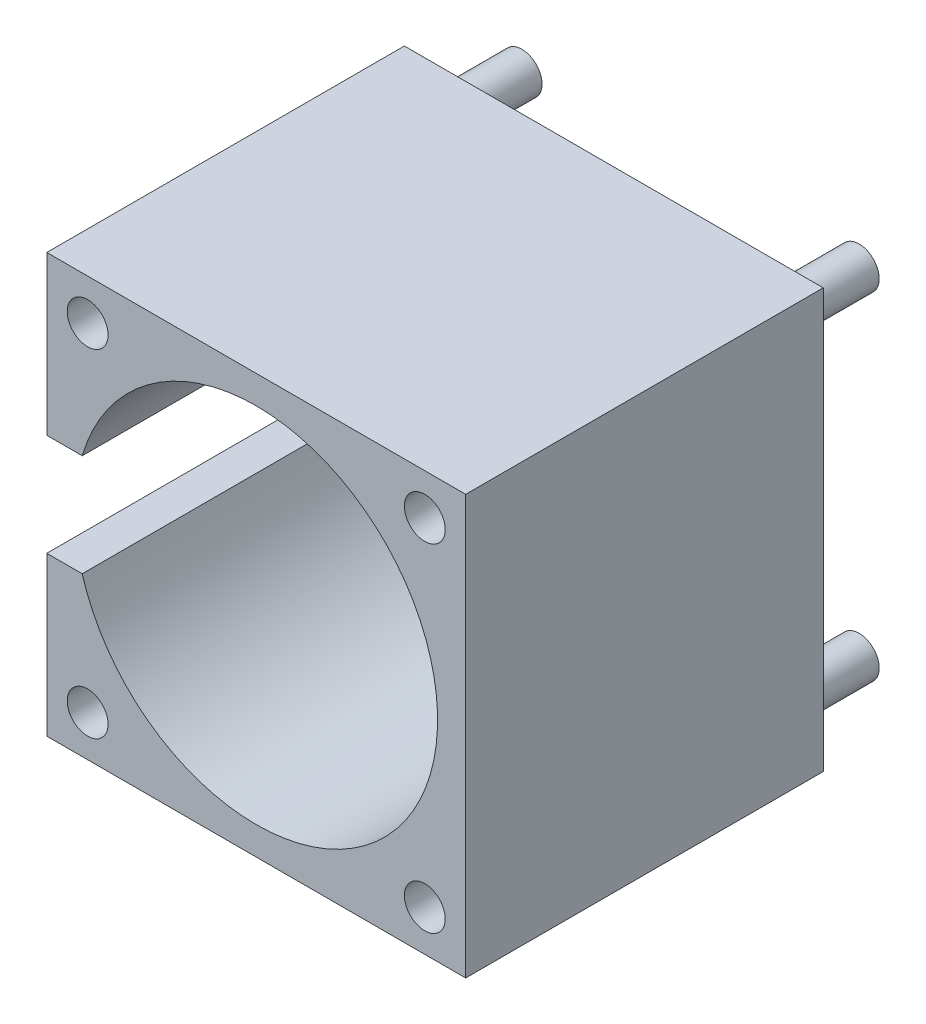
SolidWorks part; units mm, degrees
ref_plane "前基準面" through (0, 0, 0) normal (0, 0, 1) x (1, 0, 0)
ref_plane "上基準面" through (0, 0, 0) normal (0, 1, 0) x (1, 0, 0)
ref_plane "右基準面" through (0, 0, 0) normal (1, 0, 0) x (0, 0, -1)
ref_axis "基準軸1" through (0, -55, 0) along (0, 1, 0)
ref_axis "基準軸2" through (-88.99, 0, 0) along (1, 0, 0)
ref_axis "基準軸3" through (0, 0, 55) along (0, 0, -1)
sketch "草圖1" plane through (0, 0, 0) normal (0, 0, 1) x (1, 0, 0)
  line L0 (0, -55) -> (0, 55) construction
  line L1 (-41, -41) -> (41, -41)
  line L2 (-41, -41) -> (-41, 41)
  line L3 (-41, 41) -> (41, 41)
  line L4 (41, -41) -> (41, 41)
  line L5 (55, 0) -> (-55, 0) construction
  circle A0 centre (0, 0) radius 35.5
  point P7 (0, -41)
  point P10 (41, 0)
  dimension "D1" = 71
  dimension "D2" = 82
  dimension "D3" = 82
extrude "填料-伸長1" add sketch "草圖1" along normal blind 70
sketch "草圖2" plane through (0, 0, 0) normal (0, 0, -1) x (-1, 0, 0)
  line L1 (-41, 41) -> (41, 41)
  line L2 (-41, 41) -> (-41, -41)
  line L3 (-41, -41) -> (41, -41)
  line L4 (41, 41) -> (41, -41)
sketch "草圖3" plane through (0, 0, 70) normal (0, 0, 1) x (1, 0, 0)
  line L0 (-41, 41) -> (-41, -41) construction
  line L1 (-41, 10) -> (-33, 10)
  line L2 (-41, 10) -> (-41, -10)
  line L3 (-41, -10) -> (-33, -10)
  line L4 (-33, 10) -> (-33, -10)
  line L6 (45.1, 0) -> (-45.1, 0) construction
  point P6 (-33, 0)
  dimension "D1" = 8
  dimension "D2" = 20
sketch "草圖4" plane through (0, 0, 70) normal (0, 0, 1) x (1, 0, 0)
  line L1 (41, 41) -> (-41, 41) construction
  line L2 (-41, 41) -> (-41, -41) construction
  line L3 (-41, -41) -> (41, -41) construction
  line L4 (-41, 41) -> (-41, -41) construction
  circle A0 centre (-33, 33) radius 4
  circle A1 centre (33, 33) radius 4
  circle A2 centre (33, -33) radius 4
  circle A3 centre (-33, -33) radius 4
  point P15 (0, 0)
  dimension "D1" = 8
  dimension "D5" = 8
  dimension "D2" = 8
  dimension "D3" = 8
  dimension "D6" = 8
  dimension "D4" = 4
extrude "除料-伸長2" cut sketch "草圖4" against normal blind 20
fillet "圓角2" radius 3 1 edges at (-29, 33, 50)
fillet "圓角3" radius 3 1 edges at (37, 33, 50)
fillet "圓角4" radius 3 1 edges at (-29, -33, 50)
fillet "圓角5" radius 3 1 edges at (37, -33, 50)
ref_plane "平面2" through (0, 35, 0) normal (0, 1, 0) x (1, 0, 0)
extrude "除料-伸長3" cut sketch "草圖3" against normal up to next
sketch "草圖5" plane through (0, 0, 0) normal (0, 0, -1) x (-1, 0, 0)
  line L0 (41, 41) -> (41, -41) construction
  line L1 (-41, 41) -> (41, 41) construction
  line L2 (-41, 41) -> (-41, -41) construction
  line L3 (38.5, 0) -> (-38.5, 0) construction
  circle A0 centre (33, 33) radius 3.95
  circle A1 centre (-33, 33) radius 3.95
  circle A2 centre (33, -33) radius 3.95
  circle A3 centre (-33, -33) radius 3.95
  dimension "D1" = 7.9
  dimension "D4" = 7.9
  dimension "D2" = 8
  dimension "D3" = 8
  dimension "D5" = 8
  dimension "D6" = 8
extrude "填料-伸長2" add sketch "草圖5" along normal blind 15
